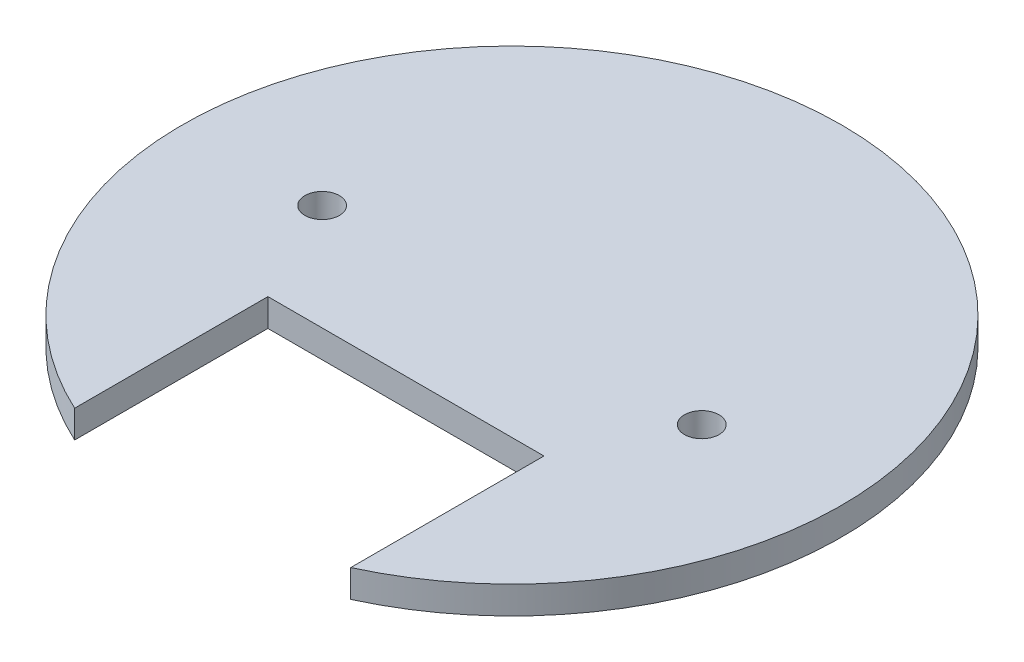
SolidWorks part; units mm, degrees
ref_plane "Front Plane" through (0, 0, 0) normal (0, 0, 1) x (1, 0, 0)
ref_plane "Top Plane" through (0, 0, 0) normal (0, 1, 0) x (1, 0, 0)
ref_plane "Right Plane" through (0, 0, 0) normal (1, 0, 0) x (0, 0, -1)
sketch "Sketch1" plane through (0, 0, 0) normal (0, 1, 0) x (1, 0, 0)
  line L0 (-47.75, 0) -> (47.75, 0) construction
  line L1 (0, 47.75) -> (0, -47.75) construction
  line L2 (-20, -43.3597) -> (-20, -15.3597)
  line L3 (-20, -15.3597) -> (20, -15.3597)
  line L4 (20, -15.3597) -> (20, -43.3597)
  arc A0 (20, -43.3597) -> (-20, -43.3597) centre (0, 0) ccw
  circle A1 centre (-27.5, 0) radius 2.5
  circle A2 centre (27.5, 0) radius 2.5
  dimension "D1" = 95.5
  dimension "D2" = 5
  dimension "D3" = 55
  dimension "D4" = 28
  dimension "D5" = 40
extrude "Boss-Extrude2" add sketch "Sketch1" along normal blind 4
